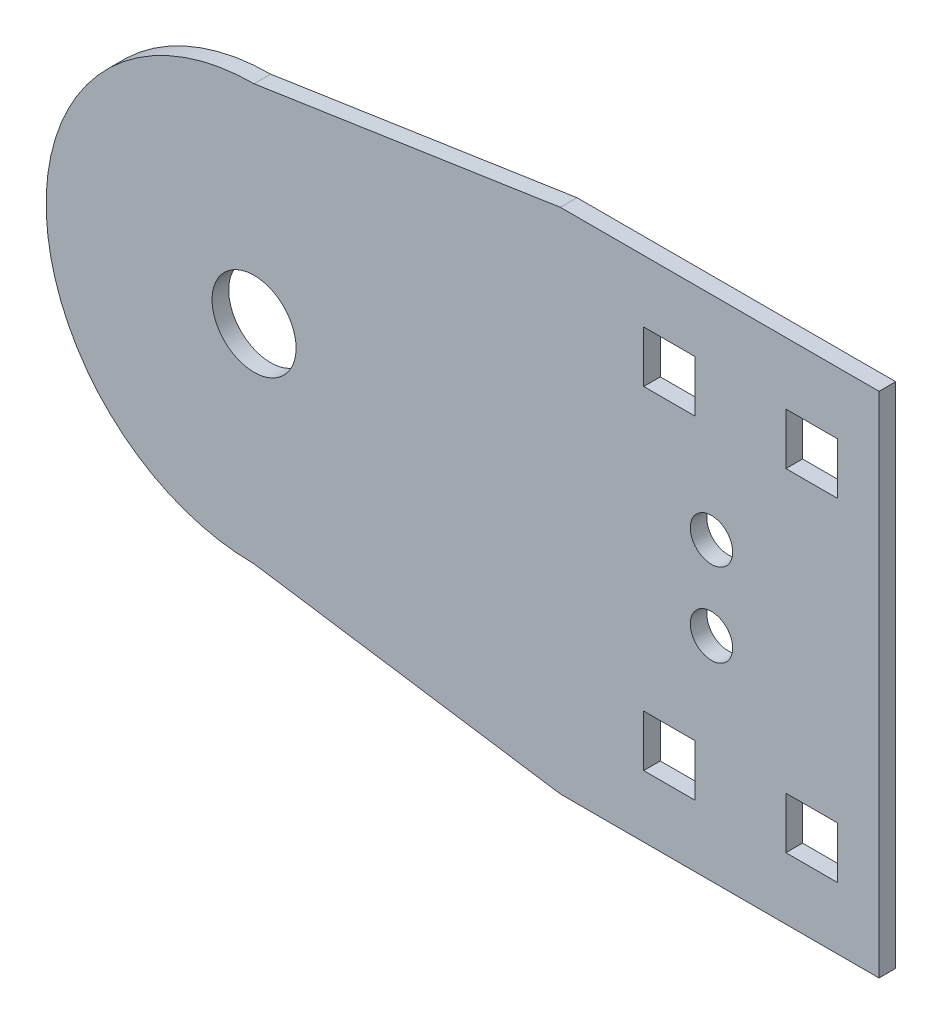
SolidWorks part; units mm, degrees
ref_plane "前视基准面" through (0, 0, 0) normal (0, 0, 1) x (1, 0, 0)
ref_plane "上视基准面" through (0, 0, 0) normal (0, 1, 0) x (1, 0, 0)
ref_plane "右视基准面" through (0, 0, 0) normal (1, 0, 0) x (0, 0, -1)
sketch "草图1" plane through (0, 0, 0) normal (0, 0, 1) x (1, 0, 0)
  line L0 (0, 0) -> (55.1994, 0) construction
  line L8 (58.5, -5) -> (58.5, -19.6678) construction
  line L9 (63.95, -16.9) -> (63.95, -23.1)
  line L10 (46.85, -16.9) -> (53.05, -16.9)
  line L11 (46.85, -16.9) -> (46.85, -23.1)
  line L12 (46.85, -23.1) -> (53.05, -23.1)
  line L13 (53.05, -16.9) -> (53.05, -23.1)
  line L14 (46.85, -16.9) -> (53.05, -23.1) construction
  line L15 (46.85, -23.1) -> (53.05, -16.9) construction
  line L16 (70.15, -23.1) -> (63.95, -23.1)
  line L17 (70.15, -16.9) -> (70.15, -23.1)
  line L18 (70.15, -16.9) -> (63.95, -16.9)
  line L19 (53.05, 16.9) -> (53.05, 23.1)
  line L20 (46.85, 23.1) -> (53.05, 23.1)
  line L21 (46.85, 16.9) -> (53.05, 16.9)
  line L22 (46.85, 16.9) -> (46.85, 23.1)
  line L23 (63.95, 16.9) -> (63.95, 23.1)
  line L24 (70.15, 23.1) -> (63.95, 23.1)
  line L25 (70.15, 16.9) -> (70.15, 23.1)
  line L26 (70.15, 16.9) -> (63.95, 16.9)
  line L27 (0, -25) -> (36.8229, -30.548)
  line L28 (36.8229, -30.548) -> (75.15, -30.548)
  line L29 (36.8229, 30.548) -> (75.15, 30.548)
  line L30 (0, 25) -> (36.8229, 30.548)
  line L31 (75.15, -30.548) -> (75.15, 30.548)
  line L32 (55, -5) -> (55, 5) construction
  circle A0 centre (0, 0) radius 5.05
  circle A1 centre (55, 5) radius 2.55
  circle A5 centre (55, -5) radius 2.55
  circle A6 centre (0, 0) radius 25 construction
  arc A7 (0, 25) -> (0, -25) centre (0, 0) ccw
  circle A8 centre (0, 0) radius 40 construction
  point P10 (49.95, -20)
  point P22 (67.05, -20)
  point P31 (67.05, 20)
  dimension "D1" = 10.1
  dimension "D5" = 55
  dimension "D6" = 6.2
  dimension "D9" = 80
  dimension "D2" = 5
  dimension "D3" = 3.5
  dimension "D4" = 6.2
  dimension "D7" = 17.1
  dimension "D8" = 40
  dimension "D10" = 5
extrude "凸台-拉伸1" add sketch "草图1" along normal blind 2
